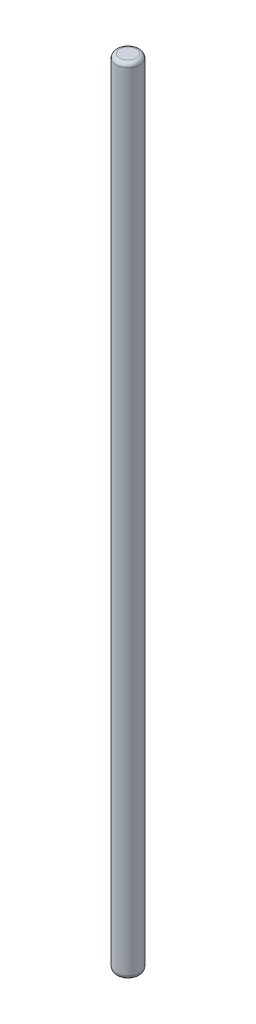
SolidWorks part; units mm, degrees
material "1023 Carbon Steel Sheet (SS)"
ref_plane "Front Plane" through (0, 0, 0) normal (0, 0, 1) x (1, 0, 0)
ref_plane "Top Plane" through (0, 0, 0) normal (0, 1, 0) x (1, 0, 0)
ref_plane "Right Plane" through (0, 0, 0) normal (1, 0, 0) x (0, 0, -1)
sketch "Sketch1" plane through (0, 0, 0) normal (0, 1, 0) x (1, 0, 0)
  circle A0 centre (0, 0) radius 2.3813
  dimension "D1" = 4.7625
extrude "Boss-Extrude1" add sketch "Sketch1" along normal blind 158.75
fillet "Fillet1" radius 0.762 2 edges at (0, 0, 2.3813) (0, 158.75, 2.3813)
